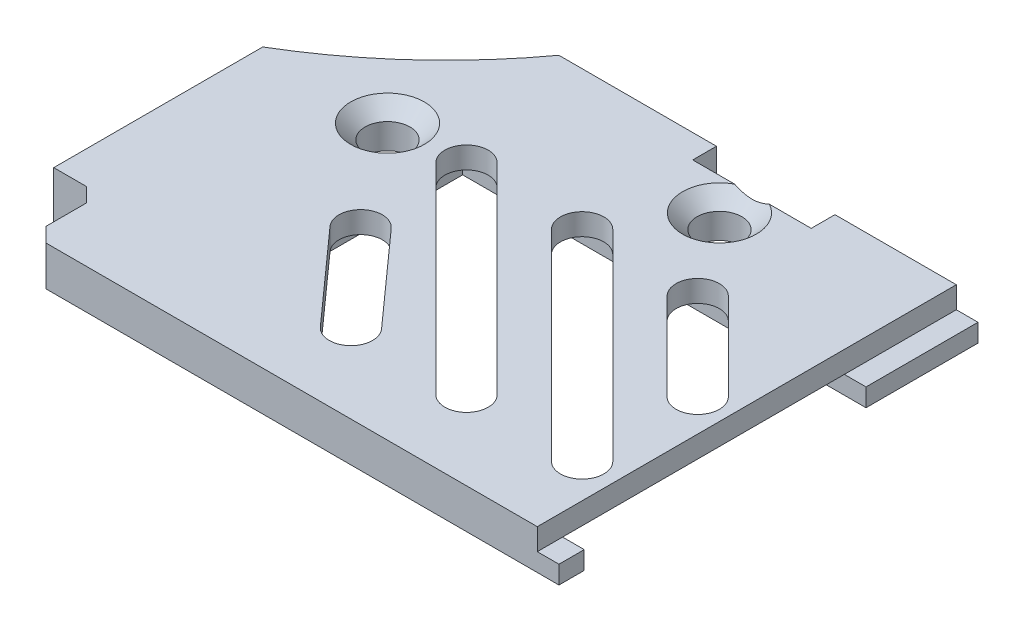
SolidWorks part; units mm, degrees
material "PPS"
ref_plane "前视基准面" through (0, 0, 0) normal (0, 0, 1) x (1, 0, 0)
ref_plane "上视基准面" through (0, 0, 0) normal (0, 1, 0) x (1, 0, 0)
ref_plane "右视基准面" through (0, 0, 0) normal (1, 0, 0) x (0, 0, -1)
sketch "基座草图-前" plane through (0, 0, 0) normal (0, 1, 0) x (1, 0, 0)
  line L2 (-24.7152, 2.0807) -> (-24.5, 0.3125)
  line L6 (-22.5, -14.2499) -> (-22.5, -7.2636)
  line L8 (-22.5, -7.2636) -> (-24.5, -7.2636)
  line L9 (-24.5, -7.2636) -> (-24.5, 0.3125)
  line L10 (-24.5, 0.3125) -> (-25.1116, 5.3379) construction
  line L12 (-26.5, 1.2398) -> (-26.5, -14.2499)
  line L13 (-26.5, -14.2499) -> (-22.5, -14.2499)
  line L16 (-4.1009, 11.812) -> (-4.1009, 8.358) construction
  line L17 (-4.1009, 8.358) -> (4.1009, 8.358)
  line L18 (4.1009, 8.358) -> (4.1009, 11.8106) construction
  line L19 (-16.253, 10) -> (-4.1009, 10)
  line L20 (-4.1009, 10) -> (-4.1009, 8.358)
  line L21 (4.1009, 8.358) -> (4.1009, 10)
  line L22 (0, 0.0001) -> (0, -23.6618) construction
  line L24 (4.1009, 10) -> (12.5, 10)
  line L25 (12.5, 10) -> (12.5, -14.2499)
  line L26 (12.5, -14.2499) -> (-26.5, -14.2499)
  arc A1 (-26.5, 2.4898) -> (-24.8662, 3.3216) centre (-28.6129, 8.6608) ccw construction
  arc A3 (-25.1116, 5.3379) -> (-57.77, 17.2644) centre (-45.4537, 0.3125) ccw construction
  arc A4 (-26.5, 1.2398) -> (-24.7152, 2.0807) centre (-28.3556, 7.493) ccw
  arc A5 (-17.503, 10) -> (-24.8662, 3.3216) centre (-44.5319, 32.4021) cw
  arc A6 (-16.253, 10) -> (-24.7152, 2.0807) centre (-44.1427, 31.321) cw
  circle A7 centre (0, 6.108) radius 1.55
  circle A8 centre (-16.866, 0) radius 1.55
  dimension "D1" = 1.25
  dimension "D2" = 1.25
  dimension "D3" = 1.25
  dimension "D4" = 16.866
  dimension "D5" = 12.5
  dimension "D6" = 9.9999
  dimension "D7" = 14.25
  dimension "D8" = 22.5
  dimension "D9" = 26.5
  dimension "D10" = 24.5
  dimension "D11" = 7.2637
extrude "基座-前" add sketch "基座草图-前" along normal blind 2.75 contours L19 A6 L2 L9 L8 L6 L26 L25 L24 L21 L17 L20 A8 A7 region at (-5.0831, 0, 2.6655)
sketch "基座草图-后" plane through (0, 0, 0) normal (0, 1, 0) x (1, 0, 0)
  line L0 (-22.5, -14.2499) -> (-22.5, -18.9999)
  line L1 (-22.5, -18.9999) -> (12.5, -18.9999)
  line L2 (12.5, -18.9999) -> (12.5, -14.2499)
  line L3 (12.5, 10) -> (12.5, -14.2499) construction
  line L4 (12.5, -14.2499) -> (-22.5, -14.2499) construction
  line L5 (-22.5, -14.2499) -> (12.5, -14.2499)
  dimension "D1" = 4.75
extrude "基座-后" add sketch "基座草图-后" along normal up to surface (2.75 mm away) up to face at (-16.866, 2.75, 1.55)
sketch "卡榫草图" plane through (0, 0, 0) normal (0, 1, 0) x (1, 0, 0)
  line L0 (-24.5, -7.2636) -> (-23.5, -7.2636)
  line L1 (-22.5, -7.2636) -> (-24.5, -7.2636) construction
  line L2 (-23.5, -7.2636) -> (-23.5, -14.2136)
  line L3 (-23.5, -14.2136) -> (-24.5, -14.2136)
  line L6 (-22.5, -18.9999) -> (-22.5, -7.2636) construction
  line L7 (-24.5, -14.2136) -> (-25.75, -14.2136)
  line L8 (-25.75, -14.2136) -> (-25.75, 0.3125)
  line L9 (-25.75, 0.3125) -> (-24.5, 0.3125) construction
  line L11 (-24.5, -7.2636) -> (-24.5, 0.3125) construction
  line L12 (-24.5, -7.2636) -> (-24.5, 0.3125)
  line L13 (-24.5, -7.2636) -> (-24.5, -14.2136)
  line L14 (-23.5, -7.2636) -> (-22.5, -7.2636)
  line L15 (-22.5, -7.2636) -> (-22.5, -14.2136)
  line L16 (-22.5, -14.2136) -> (-23.5, -14.2136)
  line L17 (-25.75, 0.3125) -> (-26.2135, 4.1214) construction
  line L18 (-24.7152, 2.0807) -> (-24.5, 0.3125) construction
  line L19 (-25.8753, 1.3423) -> (-25.75, 0.3125)
  line L20 (-24.7152, 2.0807) -> (-24.5, 0.3125)
  arc A0 (-24.7152, 2.0807) -> (-25.8753, 1.3423) centre (-44.1427, 31.321) cw
  arc A1 (-24.7152, 2.0807) -> (-16.253, 10) centre (-44.1427, 31.321) ccw construction
  dimension "D1" = 1
  dimension "D2" = 1.25
  dimension "D3" = 6.95
extrude "卡榫结构-1" add sketch "卡榫草图" along normal up to surface (2.75 mm away) contours L13 L12 L9 L8 L7 | L0 L13 L3 L2 | L12 L0 | L16 L15 L14 L2 region at (-25.1278, 0, 6.2521) region at (-24, 0, 10.7386) region at (-23, 0, 10.7386) up to face at (-16.866, 2.75, 1.55)
extrude "卡榫结构-2-注意PCB凸出部分" add sketch "草图5<4>" against normal blind 4 from surface contours L0 L13 L3 L2 | L13 L12 L9 L8 L7 region at (-25.1278, 0, 6.2521) region at (-24, 0, 10.7386) starting at face at (-9.4355, 0, 0.7086)
sketch "草图5<4>" plane through (0, 0, 0) normal (0, 1, 0) x (1, 0, 0) same geometry as "卡榫草图"
sketch "卡榫限位" plane through (0, 0, 0) normal (0, 1, 0) x (1, 0, 0)
  line L0 (12.5, 10) -> (14, 10)
  line L1 (14, 10) -> (14, -18.9999)
  line L2 (14, -18.9999) -> (12.5, -18.9999)
  line L3 (12.5, -18.9999) -> (12.5, 10)
  dimension "D1" = 1.5
extrude "限位结构" add sketch "卡榫限位" along normal blind 1.25
sketch "散热口位置" plane through (0, 0, 0) normal (0, 1, 0) x (1, 0, 0)
  line L0 (-13.916, -17.25) -> (-13.916, 2.25)
  line L1 (14, -18.9999) -> (14, 10) construction
  line L2 (-13.916, 2.25) -> (14, 2.25)
  line L4 (14, 2.25) -> (14, -17.25)
  line L5 (14, -17.25) -> (-13.916, -17.25)
  circle A0 centre (-16.866, 0) radius 1.55 construction
  dimension "D1" = 2.25
  dimension "D2" = 2.95
  dimension "D3" = 19.5
extrude "稳压PCB器件高度补偿" cut sketch "散热口位置" along normal blind 1.25
sketch "散热" plane through (0, 1.25, 0) normal (0, -1, 0) x (1, 0, 0)
  line L0 (0, 0) -> (24.2492, 0) construction
  line L1 (4.2339, -0.37) -> (10.2676, 5.6638) construction
  line L2 (3.1732, 0.6907) -> (9.2069, 6.7244)
  line L3 (5.2945, -1.4307) -> (11.3283, 4.6031)
  line L4 (-3.7661, -0.37) -> (10.1432, 13.5393) construction
  line L5 (-4.8268, 0.6907) -> (9.0825, 14.6)
  line L6 (-2.7055, -1.4307) -> (11.2038, 12.4787)
  line L7 (-11.7661, -0.37) -> (2.1432, 13.5393) construction
  line L8 (-12.8268, 0.6907) -> (1.0825, 14.6)
  line L9 (-10.7055, -1.4307) -> (3.2038, 12.4787)
  line L10 (4.2339, -0.37) -> (-3.7661, -0.37) construction
  line L11 (-3.7661, -0.37) -> (-11.7661, -0.37) construction
  line L12 (-5.8568, 13.5393) -> (-11.5554, 7.1695) construction
  line L13 (-4.7389, 12.5392) -> (-10.4375, 6.1694)
  line L14 (-6.9748, 14.5394) -> (-12.6734, 8.1696)
  line L15 (-5.8568, 13.5393) -> (2.1432, 13.5393) construction
  arc A0 (3.1732, 0.6907) -> (5.2945, -1.4307) centre (4.2339, -0.37) ccw
  arc A1 (11.3283, 4.6031) -> (9.2069, 6.7244) centre (10.2676, 5.6638) ccw
  arc A2 (-4.8268, 0.6907) -> (-2.7055, -1.4307) centre (-3.7661, -0.37) ccw
  arc A3 (11.2038, 12.4787) -> (9.0825, 14.6) centre (10.1432, 13.5393) ccw
  arc A4 (-12.8268, 0.6907) -> (-10.7055, -1.4307) centre (-11.7661, -0.37) ccw
  arc A5 (3.2038, 12.4787) -> (1.0825, 14.6) centre (2.1432, 13.5393) ccw
  arc A6 (-4.7389, 12.5392) -> (-6.9748, 14.5394) centre (-5.8568, 13.5393) ccw
  arc A7 (-12.6734, 8.1696) -> (-10.4375, 6.1694) centre (-11.5554, 7.1695) ccw
  point P5 (7.2507, 2.6469)
  point P14 (3.1885, 6.5847)
  point P20 (-4.8115, 6.5847)
  point P26 (-8.7061, 10.3544)
  dimension "D1" = 135
  dimension "D2" = 3
  dimension "D3" = 8
extrude "切除-拉伸2" cut sketch "散热" against normal through all
chamfer "倒角1" distance 1 angle 45 3 edges at (-20.6617, 2.75, -5.2238) (-22.5, 1.375, 18.9999) (-22.5, 1.375, 14.2136)
chamfer "倒角2" distance 1 angle 45 2 edges at (-16.866, 2.75, 1.55) (0, 2.75, -4.558)
sketch "草图1" plane through (0, -4, 0) normal (0, -1, 0) x (1, 0, 0)
  line L0 (-24.7152, -2.0807) -> (-24.5, -0.3125)
  line L1 (-24.5, -0.3125) -> (-24.5, 7.2636)
  line L2 (-24.5, 7.2636) -> (-23.5, 7.2636)
  line L3 (-23.5, 7.2636) -> (-23.5, 7.5136)
  line L4 (-23.5, 14.2136) -> (-23.5, 7.2636) construction
  line L5 (-23.5, 7.5136) -> (-24.75, 7.5136)
  line L8 (-24.9466, -1.9283) -> (-24.75, -0.3125)
  line L9 (-24.75, -0.3125) -> (-24.75, 7.5136)
  arc A0 (-24.7152, -2.0807) -> (-25.8753, -1.3423) centre (-44.1427, -31.321) ccw construction
  arc A1 (-24.9466, -1.9283) -> (-24.7152, -2.0807) centre (-44.1427, -31.321) cw
  point P18 (-24, 7.2636)
  dimension "D1" = 0.25
  dimension "D2" = 0.2482
  dimension "D3" = 0.25
extrude "公差切除" cut sketch "草图1" against normal up to surface (4 mm away) from surface up to face at (0, 0, -4.558) starting at face at (-24.7609, -4, 4.864)
